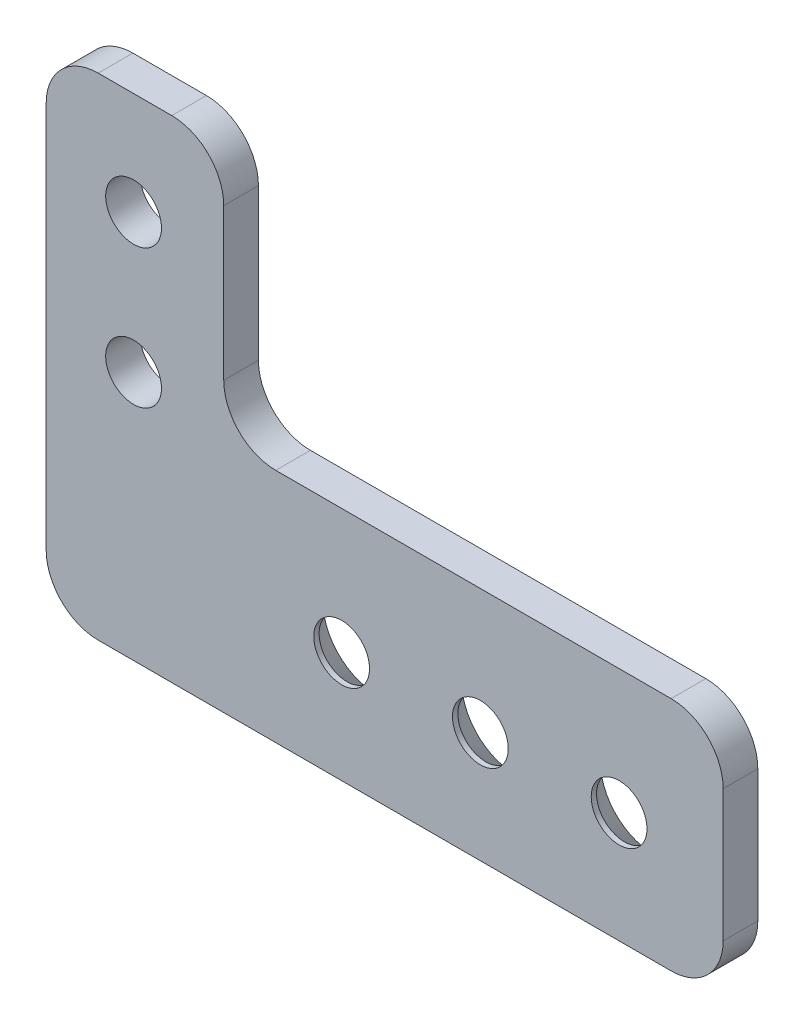
SolidWorks part; units mm, degrees
material "6061-T6 (SS)"
ref_plane "Front Plane" through (0, 0, 0) normal (0, 0, 1) x (1, 0, 0)
ref_plane "Top Plane" through (0, 0, 0) normal (0, 1, 0) x (1, 0, 0)
ref_plane "Right Plane" through (0, 0, 0) normal (1, 0, 0) x (0, 0, -1)
sketch "Sketch1" plane through (0, 0, 0) normal (0, 0, 1) x (1, 0, 0)
  line L0 (34.925, -11.049) -> (-27.051, -11.049) construction
  line L1 (-34.925, -23.749) -> (34.925, -23.749)
  line L2 (-34.925, -23.749) -> (-34.925, 23.749)
  line L3 (-34.925, 23.749) -> (34.925, 23.749)
  line L4 (34.925, -23.749) -> (34.925, 23.749)
  line L5 (-34.925, -23.749) -> (34.925, 23.749) construction
  line L6 (-34.925, 23.749) -> (34.925, -23.749) construction
  line L7 (34.925, 23.749) -> (-10.795, 23.749)
  line L8 (34.925, 23.749) -> (34.925, 0.381)
  line L9 (34.925, 0.381) -> (-10.795, 0.381)
  line L10 (-10.795, 23.749) -> (-10.795, 0.381)
  line L11 (-34.925, -23.749) -> (-27.051, -23.749)
  line L12 (-34.925, -23.749) -> (-34.925, 23.749)
  line L13 (-34.925, 23.749) -> (-27.051, 23.749)
  line L14 (-27.051, -23.749) -> (-27.051, 23.749)
  line L15 (-27.051, -23.749) -> (34.925, -23.749)
  line L16 (-27.051, -23.749) -> (-27.051, -21.209)
  line L17 (-27.051, -21.209) -> (34.925, -21.209)
  line L18 (34.925, -23.749) -> (34.925, -21.209)
  line L19 (-27.051, 23.876) -> (-10.795, 23.876) construction
  circle A0 centre (-19.05, -11.049) radius 2.5527
  circle A1 centre (-19.05, 1.651) radius 2.5527
  circle A2 centre (-19.05, 14.351) radius 2.5527
  point P0 (0, 0)
  point P22 (25.4, -11.049)
  point P23 (0, -11.049)
  point P24 (12.7, -11.049)
  dimension "D7" = 5.1054
  dimension "D1" = 69.85
  dimension "D2" = 47.498
  dimension "D3" = 24.13
  dimension "D4" = 24.13
  dimension "D5" = 7.874
  dimension "D6" = 47.498
  dimension "D8" = 15.875
  dimension "D9" = 12.7
  dimension "D10" = 12.7
  dimension "D11" = 12.7
  dimension "D12" = 9.525
  dimension "D13" = 12.7
  dimension "D14" = 12.7
  dimension "D15" = 27.051
  dimension "D16" = 2.54
extrude "Boss-Extrude1" add sketch "Sketch1" along normal blind 3.175 contours L14 L17 L4 L9 L10 L3 A2 A1 A0 | A0 region at (-0.453, -5.7065, 0) region at (-19.05, -11.049, 0)
fillet "Fillet1" radius 4.7625 6 edges at (-27.051, 23.749, 1.5875) (-10.795, 23.749, 1.5875) (-10.795, 0.381, 1.5875) (34.925, 0.381, 1.5875) (34.925, -21.209, 1.5875) (-27.051, -21.209, 1.5875)
hole_wizard "CSK for #10 Flat Head Machine Screw3" positions "Sketch6" profile "Sketch7" countersink size "#10" standard "ANSI Inch" end condition through all
sketch "Sketch6" plane through (0, 0, 0) normal (0, 0, -1) x (-1, 0, 0)
  point P0 (-25.4, -11.049)
  point P3 (-12.7, -11.049)
  point P6 (0, -11.049)
sketch "Sketch7" plane through (25.4, -11.049, 0) normal (1, 0, 0) x (0, 1, 0)
  line L0 (0, 0) -> (0, 3.175)
  line L1 (0, 3.175) -> (2.5527, 3.175)
  line L2 (2.5527, 3.175) -> (2.5527, 2.6882)
  line L3 (2.5527, 2.6882) -> (4.8895, 0)
  line L5 (4.8895, 0) -> (0, 0)
  line L6 (-2.5527, 2.6882) -> (-4.8895, 0) construction
  line L11 (0, -6.35) -> (0, 107.95) construction
  dimension "Thru Hole Dia." = 5.1054
  dimension "Thru Hole Depth" = 3.175
  dimension "Near C'Sink Dia." = 9.779
  dimension "Near C'Sink Angle" = 82
